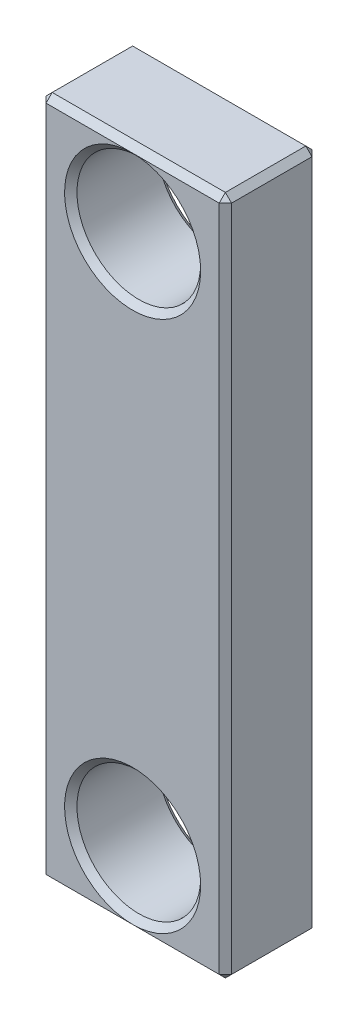
SolidWorks part; units mm, degrees
ref_plane "Front Plane" through (0, 0, 0) normal (0, 0, 1) x (1, 0, 0)
ref_plane "Top Plane" through (0, 0, 0) normal (0, 1, 0) x (1, 0, 0)
ref_plane "Right Plane" through (0, 0, 0) normal (1, 0, 0) x (0, 0, -1)
sketch "Sketch1" plane through (0, 0, 0) normal (0, 0, 1) x (1, 0, 0)
  line L1 (-15, 55) -> (15, 55)
  line L2 (-15, 55) -> (-15, -55)
  line L3 (-15, -55) -> (15, -55)
  line L4 (15, 55) -> (15, -55)
  line L5 (-15, 55) -> (15, -55) construction
  line L6 (-15, -55) -> (15, 55) construction
  circle A0 centre (0, 43) radius 10
  circle A1 centre (0, -43) radius 10
  point P0 (0, 0)
  dimension "D3" = 20
  dimension "D4" = 20
  dimension "D1" = 110
  dimension "D2" = 30
  dimension "D5" = 12
  dimension "D6" = 12
extrude "Boss-Extrude1" add sketch "Sketch1" along normal blind 15
chamfer "Chamfer1" distance 1 angle 45 16 edges at (15, 55, 7.5) (-15, 55, 7.5) (-15, -55, 7.5) (0, -55, 15) (-15, 0, 15) (0, 55, 15) (15, 0, 15) (15, -55, 7.5) (0, -55, 0) (-15, 0, 0) (0, 55, 0) (15, 0, 0) (10, 43, 15) (10, 43, 0) (10, -43, 15) (10, -43, 0)
